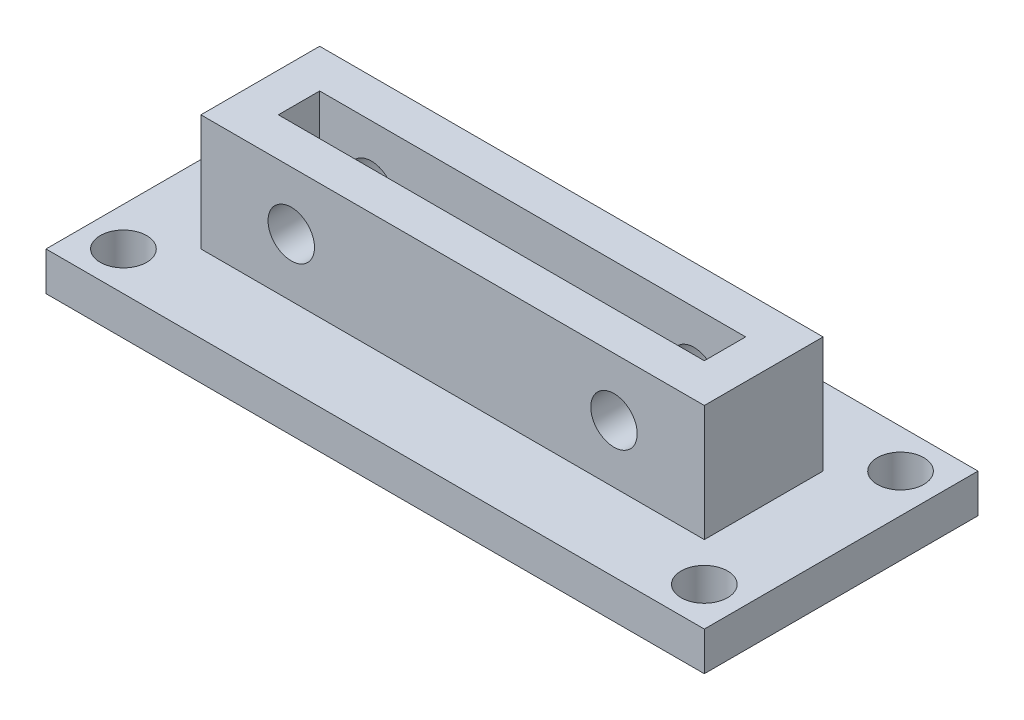
SolidWorks part; units mm, degrees
ref_plane "Front Plane" through (0, 0, 0) normal (0, 0, 1) x (1, 0, 0)
ref_plane "Top Plane" through (0, 0, 0) normal (0, 1, 0) x (1, 0, 0)
ref_plane "Right Plane" through (0, 0, 0) normal (1, 0, 0) x (0, 0, -1)
sketch "Sketch1" plane through (0, 0, 0) normal (0, 1, 0) x (1, 0, 0)
  line L1 (0, 0) -> (51, 0)
  line L2 (0, 0) -> (0, 21.2)
  line L3 (0, 21.2) -> (51, 21.2)
  line L4 (51, 0) -> (51, 21.2)
  dimension "D1" = 51
  dimension "D2" = 21.2
extrude "Boss-Extrude1" add sketch "Sketch1" along normal blind 3
sketch "Sketch2" plane through (0, 3, 0) normal (0, 1, 0) x (1, 0, 0)
  line L0 (0, 21.2) -> (0, 0) construction
  line L1 (6, 15.2) -> (45, 15.2)
  line L2 (6, 15.2) -> (6, 6)
  line L3 (6, 6) -> (45, 6)
  line L4 (45, 15.2) -> (45, 6)
  line L5 (9, 12.2) -> (42, 12.2)
  line L6 (9, 12.2) -> (9, 9)
  line L7 (9, 9) -> (42, 9)
  line L8 (42, 12.2) -> (42, 9)
  line L9 (0, 21.2) -> (0, 0) construction
  line L10 (0, 0) -> (51, 0) construction
  line L11 (0, 0) -> (51, 0) construction
  point P10 (25.5, 12.2)
  point P11 (25.5, 15.2)
  point P13 (0, 10.6)
  point P14 (6, 10.6)
  point P16 (25.5, 0)
  point P17 (25.5, 6)
  dimension "D1" = 3.2
  dimension "D2" = 3
  dimension "D3" = 3
  dimension "D4" = 33
  dimension "D5" = 39
extrude "Boss-Extrude2" add sketch "Sketch2" along normal blind 9
hole_wizard "M3 Clearance Hole1" positions "Sketch4" profile "Sketch5" hole size "M3" standard "ANSI Metric" end condition through all
sketch "Sketch4" plane through (0, 3, 0) normal (0, 1, 0) x (1, 0, 0)
  line L0 (25.5, 21.2) -> (25.5, 0) construction
  line L1 (51, 21.2) -> (0, 21.2) construction
  line L2 (0, 0) -> (51, 0) construction
  line L4 (0, 10.6) -> (51, 10.6) construction
  line L5 (0, 21.2) -> (0, 0) construction
  line L6 (51, 0) -> (51, 21.2) construction
  line L7 (6, 15.2) -> (6, 21.2) construction
  line L9 (6, 15.2) -> (0, 15.2) construction
  point P0 (3, 18.2)
  point P31 (48, 18.2)
  point P43 (5.327, 17.5)
  point P44 (5, 21.1406)
  point P45 (2.0805, 21.7705)
  point P46 (0, 0)
  point P47 (6, 18.2)
  point P48 (3, 15.2)
  point P49 (0, 0)
  point P50 (0, 0)
  point P51 (48, 3)
  point P52 (3, 3)
  dimension "D1" = 3
  dimension "D2" = 3
  dimension "D3" = 45
sketch "Sketch5" plane through (3, 3, -18.2) normal (1, 0, 0) x (0, 0, 1)
  line L0 (0, 0) -> (0, 3)
  line L1 (0, 3) -> (1.8, 3)
  line L2 (1.8, 3) -> (1.8, 0)
  line L5 (1.8, 0) -> (0, 0)
  line L11 (0, -6.35) -> (0, 107.95) construction
  dimension "Thru Hole Dia." = 3.6
  dimension "Thru Hole Depth" = 3
hole_wizard "M3 Clearance Hole2" positions "Sketch6" profile "Sketch7" hole size "M3" standard "ANSI Metric" end condition through all
sketch "Sketch6" plane through (0, 0, -6) normal (0, 0, 1) x (1, 0, 0)
  line L2 (9, 12) -> (42, 12) construction
  line L3 (9, 12) -> (42, 12) construction
  line L4 (13, 7.5) -> (38, 7.5) construction
  line L6 (9, 12) -> (9, 3) construction
  line L7 (9, 12) -> (9, 3) construction
  point P3 (13, 7.5)
  point P5 (38, 7.5)
  point P18 (25.5, 7.5)
  point P19 (25.5, 12)
  point P23 (0, 0)
  point P24 (9, 7.5)
  dimension "D1" = 4
sketch "Sketch7" plane through (13, 7.5, -6) normal (1, 0, 0) x (0, -1, 0)
  line L0 (0, 0) -> (0, 15.2)
  line L1 (0, 15.2) -> (1.8, 15.2)
  line L2 (1.8, 15.2) -> (1.8, 0)
  line L5 (1.8, 0) -> (0, 0)
  line L11 (0, -6.35) -> (0, 107.95) construction
  dimension "Thru Hole Dia." = 3.6
  dimension "Thru Hole Depth" = 15.2
equation "\"A\"=9.9176"
